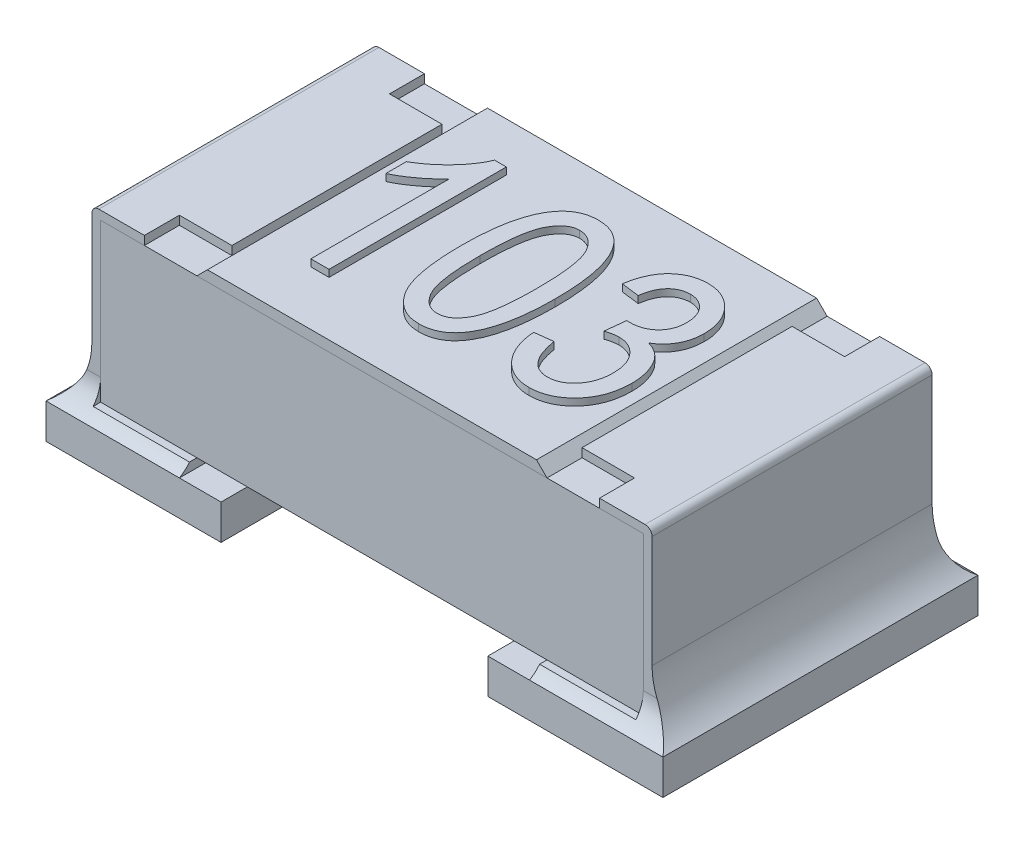
SolidWorks part; units mm, degrees
material "Ceramic Porcelain"
ref_plane "Front Plane" through (0, 0, 0) normal (0, 0, 1) x (1, 0, 0)
ref_plane "Top Plane" through (0, 0, 0) normal (0, 1, 0) x (1, 0, 0)
ref_plane "Right Plane" through (0, 0, 0) normal (1, 0, 0) x (0, 0, -1)
sketch "Sketch1" plane through (0, 0, 0) normal (1, 0, 0) x (0, 0, -1)
  line L0 (0, 55) -> (0, -55) construction
  line L1 (-0.4, 0.575) -> (0.4, 0.575)
  line L2 (-0.4, 0.575) -> (-0.4, 0.125)
  line L3 (-0.4, 0.125) -> (0.4, 0.125)
  line L4 (0.4, 0.575) -> (0.4, 0.125)
  line L5 (55, 0) -> (-55, 0) construction
  dimension "D1" = 0.8
  dimension "D2" = 0.4
  dimension "D3" = 0.45
  dimension "D4" = 0.125
extrude "Boss-Extrude1" add sketch "Sketch1" along normal mid plane 1.55
sketch "Sketch2" plane through (0, 0, 0) normal (0, 0, 1) x (1, 0, 0)
  line L0 (-0.5, 0.6) -> (-0.78, 0.6)
  line L1 (-0.8, 0.58) -> (-0.8, 0.1)
  line L2 (-0.8, 0.1) -> (-0.5, 0.1)
  line L3 (-0.5, 0.1) -> (-0.5, 0.125)
  line L4 (0.775, 0.125) -> (-0.775, 0.125) construction
  line L5 (-0.5, 0.125) -> (-0.775, 0.125)
  line L6 (-0.775, 0.125) -> (-0.775, 0.575)
  line L7 (-0.775, 0.575) -> (-0.5, 0.575)
  line L8 (0.775, 0.575) -> (-0.775, 0.575) construction
  line L9 (-0.5, 0.575) -> (-0.5, 0.6)
  line L11 (0.5, 0.575) -> (0.5, 0.6)
  line L12 (0.5, 0.6) -> (0.78, 0.6)
  line L13 (0.8, 0.58) -> (0.8, 0.1)
  line L14 (0.8, 0.1) -> (0.5, 0.1)
  line L15 (0.5, 0.1) -> (0.5, 0.125)
  line L16 (0.5, 0.125) -> (0.775, 0.125)
  line L17 (0.775, 0.125) -> (0.775, 0.575)
  line L18 (0.775, 0.575) -> (0.5, 0.575)
  arc A0 (0.78, 0.6) -> (0.8, 0.58) centre (0.78, 0.58) cw
  arc A1 (-0.78, 0.6) -> (-0.8, 0.58) centre (-0.78, 0.58) ccw
  point P28 (-0.8, 0.6)
  dimension "D6" = 0.02
  dimension "D1" = 0.025
  dimension "D2" = 0.025
  dimension "D3" = 0.025
  dimension "D4" = 0.3
  dimension "D5" = 0.3
extrude "Boss-Extrude2" add sketch "Sketch2" along normal mid plane 0.8 separate body
sketch "Sketch3" plane through (0, 0.6, 0) normal (0, 1, 0) x (1, 0, 0)
  line L0 (0.5, -0.4) -> (0.5, 0.4) construction
  line L1 (-0.5, 0.4) -> (-0.65, 0.4)
  line L2 (-0.5, 0.4) -> (-0.5, 0.3)
  line L3 (-0.5, 0.3) -> (-0.65, 0.3)
  line L4 (-0.65, 0.4) -> (-0.65, 0.3)
  line L5 (-0.5, -0.4) -> (-0.65, -0.4)
  line L6 (-0.5, -0.4) -> (-0.5, -0.3)
  line L7 (-0.5, -0.3) -> (-0.65, -0.3)
  line L8 (-0.65, -0.4) -> (-0.65, -0.3)
  line L9 (0.5, -0.4) -> (0.65, -0.4)
  line L10 (0.5, -0.4) -> (0.5, -0.3)
  line L11 (0.5, -0.3) -> (0.65, -0.3)
  line L12 (0.65, -0.4) -> (0.65, -0.3)
  line L13 (0.775, -0.4) -> (-0.775, -0.4) construction
  line L15 (0.5, 0.4) -> (0.65, 0.4)
  line L16 (0.5, 0.4) -> (0.5, 0.3)
  line L17 (0.5, 0.3) -> (0.65, 0.3)
  line L18 (0.65, 0.4) -> (0.65, 0.3)
  dimension "D1" = 0.15
  dimension "D2" = 0.1
extrude "Cut-Extrude1" cut sketch "Sketch3" against normal blind 0.025
sketch "Sketch4" plane through (0, 0, 0) normal (0, 0, 1) x (1, 0, 0)
  line L0 (-0.5, 0.575) -> (0.5, 0.575)
  line L1 (0.5, 0.575) -> (0.47, 0.605)
  line L2 (0.47, 0.605) -> (-0.47, 0.605)
  line L3 (-0.47, 0.605) -> (-0.5, 0.575)
  dimension "D1" = 45
  dimension "D2" = 45
  dimension "D3" = 0.03
extrude "Boss-Extrude3" add sketch "Sketch4" along normal mid plane 0.8 separate body
sketch "Sketch7" plane through (0, 0, 0) normal (0, 1, 0) x (1, 0, 0)
  line L0 (0, -0.2777) -> (0, 0.2777) construction
  line L1 (-0.381, -0.45) -> (-0.881, -0.45)
  line L2 (-0.381, -0.45) -> (-0.381, 0.45)
  line L3 (-0.381, 0.45) -> (-0.881, 0.45)
  line L4 (-0.881, -0.45) -> (-0.881, 0.45)
  line L5 (0.381, -0.45) -> (0.881, -0.45)
  line L6 (0.381, -0.45) -> (0.381, 0.45)
  line L7 (0.381, 0.45) -> (0.881, 0.45)
  line L8 (0.881, -0.45) -> (0.881, 0.45)
  line L9 (-0.2777, 0) -> (0.2777, 0) construction
  dimension "D1" = 0.5
  dimension "D2" = 0.381
  dimension "D3" = 0.381
  dimension "D4" = 0.9
  dimension "D5" = 0.45
extrude "Boss-Extrude5" add sketch "Sketch7" along normal blind 0.1
fillet "Fillet3" radius 0.2 1 edges at (-0.8, 0.1, 0)
fillet "Fillet4" radius 0.2 1 edges at (0.8, 0.1, 0)
fillet "Fillet5" radius 0.1 2 edges at (0.6905, 0.1, -0.4) (0.6905, 0.1, 0.4)
fillet "Fillet6" radius 0.1 2 edges at (-0.6905, 0.1, 0.4) (-0.6905, 0.1, -0.4)
sketch "Esquisse2" plane through (0, 0.605, 0) normal (0, 1, 0) x (1, 0, 0)
  text T0 "103\r\n" font "Arial Narrow" height 0.5
extrude "Boss.-Extru.1" add sketch "Esquisse2" along normal blind 0.02
